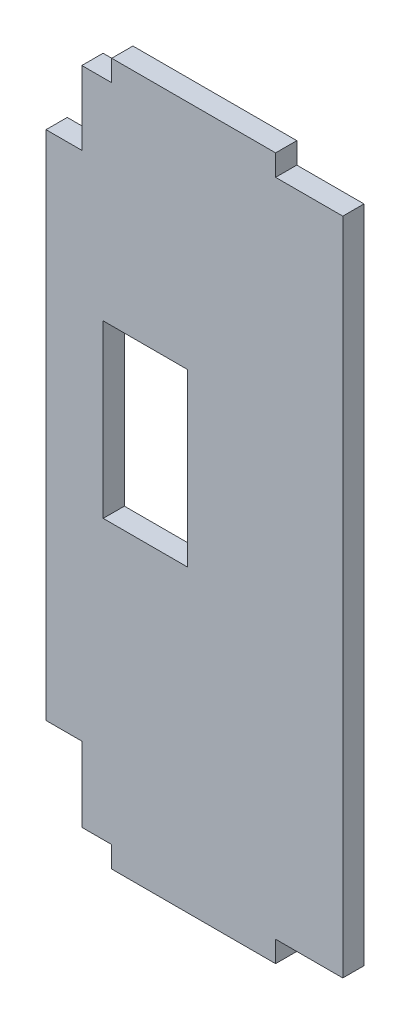
SolidWorks part; units mm, degrees
ref_plane "Front Plane" through (0, 0, 0) normal (0, 0, 1) x (1, 0, 0)
ref_plane "Top Plane" through (0, 0, 0) normal (0, 1, 0) x (1, 0, 0)
ref_plane "Right Plane" through (0, 0, 0) normal (1, 0, 0) x (0, 0, -1)
sketch "Sketch1" plane through (0, 0, 0) normal (0, 0, 1) x (1, 0, 0)
  line L0 (-14.732, -1.8034) -> (-5.715, -1.8034) construction
  line L1 (-15.6337, -19.7104) -> (-8.4455, -19.7104)
  line L2 (-15.6337, -19.7104) -> (-15.6337, -34.2646)
  line L3 (-15.6337, -34.2646) -> (-8.4455, -34.2646)
  line L4 (-8.4455, -19.7104) -> (-8.4455, -34.2646)
  line L6 (-17.4498, -1.8034) -> (-17.4498, -8.0561)
  line L7 (-17.4498, -8.0561) -> (-20.4978, -8.0561)
  line L8 (-20.4978, -8.0561) -> (-20.4978, -51.5874)
  line L9 (-20.4978, -51.5874) -> (-17.4498, -51.5874)
  line L10 (-17.4498, -51.5874) -> (-17.4498, -57.9374)
  line L11 (-17.4498, -1.8034) -> (-14.9098, -1.8034)
  line L12 (-14.9098, -1.8034) -> (-14.9098, 0)
  line L13 (-14.9098, 0) -> (-0.9652, 0)
  line L14 (-0.9652, 0) -> (-0.9652, -1.8034)
  line L15 (-0.9652, -1.8034) -> (4.7498, -1.8034)
  line L16 (4.7498, -1.8034) -> (4.7498, -57.9374)
  line L18 (4.7498, -57.9374) -> (-0.9652, -57.9374)
  line L19 (-0.9652, -57.9374) -> (-0.9652, -59.7408)
  line L20 (-0.9652, -59.7408) -> (-14.9098, -59.7408)
  line L21 (-14.9098, -59.7408) -> (-14.9098, -57.9374)
  line L22 (-14.9098, -57.9374) -> (-17.4498, -57.9374)
  line L23 (-20.4978, -1.8034) -> (-20.4978, -8.0561) construction
  dimension "D1" = 17.907
  dimension "D2" = 7.1882
  dimension "D3" = 14.5542
  dimension "D4" = 9.0043
  dimension "D5" = 3.048
extrude "Boss-Extrude1" add sketch "Sketch1" along normal blind 1.8034
